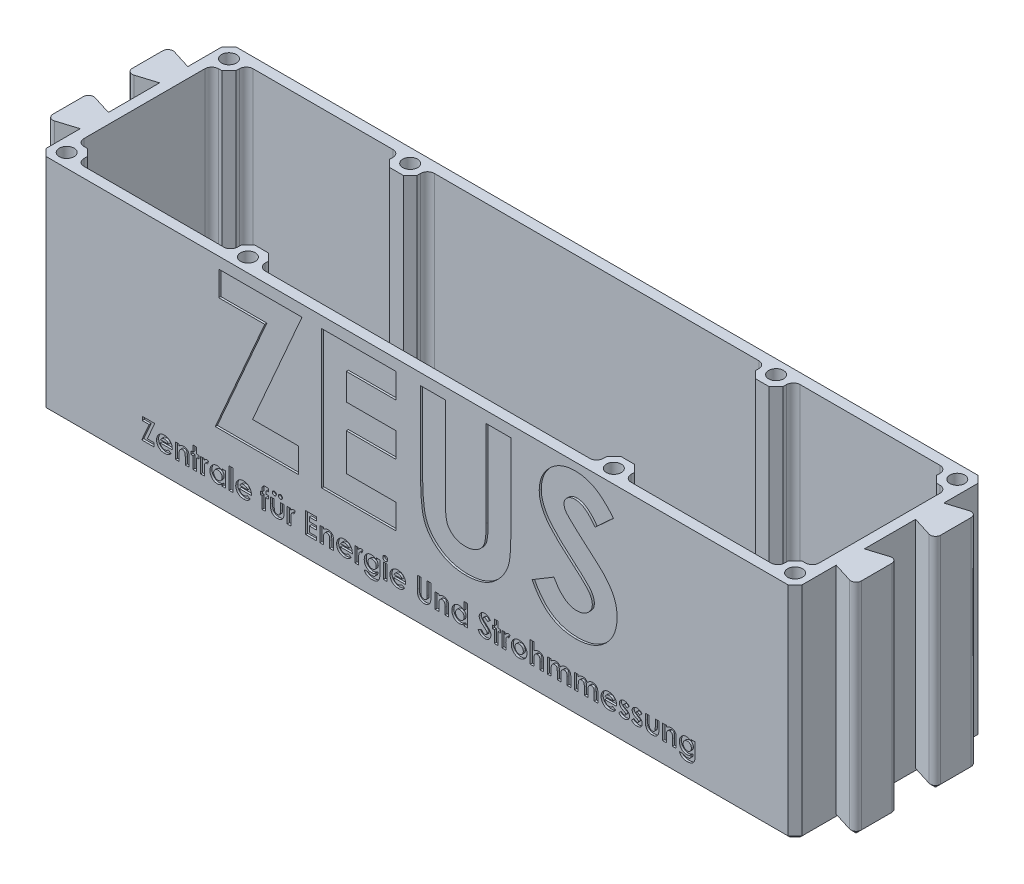
SolidWorks part; units mm, degrees
material "ABS"
ref_plane "Front Plane" through (0, 0, 0) normal (0, 0, 1) x (1, 0, 0)
ref_plane "Top Plane" through (0, 0, 0) normal (0, 1, 0) x (1, 0, 0)
ref_plane "Right Plane" through (0, 0, 0) normal (1, 0, 0) x (0, 0, -1)
sketch "Sketch1" plane through (0, 0, 0) normal (0, 1, 0) x (1, 0, 0)
  line L1 (0, 0) -> (219, 0)
  line L2 (0, 0) -> (0, 55)
  line L3 (0, 55) -> (219, 55)
  line L4 (219, 0) -> (219, 55)
  dimension "D1" = 55
  dimension "D2" = 219
extrude "baseplate" add sketch "Sketch1" along normal blind 4
sketch "Sketch2" plane through (0, 4, 0) normal (0, 1, 0) x (1, 0, 0)
  line L0 (83.3935, 27.5) -> (88.6435, 27.5) construction
  line L1 (83.3935, 49) -> (141.3935, 49) construction
  line L2 (83.3935, 49) -> (83.3935, 6) construction
  line L3 (83.3935, 6) -> (141.3935, 6) construction
  line L4 (141.3935, 49) -> (141.3935, 6) construction
  line L5 (88.6435, 27.5) -> (136.1435, 27.5) construction
  line L6 (136.1435, 27.5) -> (141.3935, 27.5) construction
  line L7 (83.3935, 27.5) -> (0, 27.5) construction
  line L8 (0, 55) -> (0, 0) construction
  line L10 (3, 52) -> (3, 3)
  line L11 (3, 3) -> (216, 3)
  line L12 (216, 3) -> (216, 52)
  line L13 (216, 52) -> (3, 52)
  line L14 (0, 55) -> (0, 0)
  line L15 (0, 0) -> (219, 0)
  line L16 (219, 0) -> (219, 55)
  line L17 (219, 55) -> (0, 55)
  line L18 (0, 55) -> (0, 0)
  line L19 (0, 0) -> (219, 0)
  line L20 (219, 0) -> (219, 55)
  line L21 (219, 55) -> (0, 55)
  circle A0 centre (88.6435, 27.5) radius 2.25 construction
  circle A1 centre (136.1435, 27.5) radius 2.25 construction
  dimension "D3" = 47.5
  dimension "D4" = 4.5
  dimension "D1" = 58
  dimension "D2" = 43
  dimension "D5" = 0
  dimension "D6" = 3
extrude "wall" add sketch "Sketch2" along normal blind 60
chamfer "wall_chamfer" distance 2 angle 45 8 edges at (0, 32, -55) (0, 32, 0) (219, 32, 0) (219, 32, -55) (216, 34, -3) (216, 34, -52) (3, 34, -3) (3, 34, -52)
sketch "Sketch3" plane through (0, 64, 0) normal (0, 1, 0) x (1, 0, 0)
  line L0 (0, 43.081) -> (-5.6527, 44.847)
  line L1 (0, 53) -> (0, 2) construction
  line L2 (-7.6, 43.4153) -> (-7.6, 34.5847)
  line L3 (-5.6527, 33.153) -> (0, 34.919)
  line L4 (0, 34.919) -> (0, 43.081)
  line L5 (109.5, 55) -> (109.5, 3) construction
  line L6 (217, 55) -> (2, 55) construction
  line L7 (5, 3) -> (214, 3) construction
  line L8 (0, 11.919) -> (0, 20.081)
  line L9 (0, 20.081) -> (-5.6527, 21.847)
  line L10 (-7.6, 20.4153) -> (-7.6, 11.5847)
  line L11 (-5.6527, 10.153) -> (0, 11.919)
  line L12 (0, 2) -> (0, 11.919) construction
  line L13 (0, 43.081) -> (0, 53) construction
  line L14 (224.6527, 33.153) -> (219, 34.919)
  line L15 (226.6, 43.4153) -> (226.6, 34.5847)
  line L16 (219, 43.081) -> (224.6527, 44.847)
  line L17 (219, 34.919) -> (219, 43.081)
  line L18 (224.6527, 10.153) -> (219, 11.919)
  line L19 (226.6, 20.4153) -> (226.6, 11.5847)
  line L20 (219, 20.081) -> (224.6527, 21.847)
  line L21 (219, 11.919) -> (219, 20.081)
  arc A0 (-5.6527, 44.847) -> (-7.6, 43.4153) centre (-6.1, 43.4153) ccw
  arc A1 (-5.6527, 33.153) -> (-7.6, 34.5847) centre (-6.1, 34.5847) cw
  arc A2 (-5.6527, 21.847) -> (-7.6, 20.4153) centre (-6.1, 20.4153) ccw
  arc A3 (-5.6527, 10.153) -> (-7.6, 11.5847) centre (-6.1, 11.5847) cw
  arc A4 (224.6527, 33.153) -> (226.6, 34.5847) centre (225.1, 34.5847) ccw
  arc A5 (224.6527, 44.847) -> (226.6, 43.4153) centre (225.1, 43.4153) cw
  arc A6 (224.6527, 10.153) -> (226.6, 11.5847) centre (225.1, 11.5847) ccw
  arc A7 (224.6527, 21.847) -> (226.6, 20.4153) centre (225.1, 20.4153) cw
  dimension "D3" = 1.5
  dimension "D1" = 7.6
  dimension "D2" = 34.7
  dimension "D4" = 2
  dimension "D5" = 23
  dimension "D6" = 8.162
extrude "dovetails" add sketch "Sketch3" against normal up to surface (64 mm away) up to face at (109.5, 0, -27.5)
chamfer "dovetail_chamfers" distance 1.5 angle 45 20 edges at (221.8263, 0, -11.036) (225.9885, 0, -10.3762) (226.6, 0, -16) (225.9885, 0, -21.6238) (221.8263, 0, -20.964) (221.8263, 0, -34.036) (225.9885, 0, -33.3762) (226.6, 0, -39) (225.9885, 0, -44.6238) (221.8263, 0, -43.964) (-2.8263, 0, -43.964) (-6.9885, 0, -44.6238) (-7.6, 0, -39) (-6.9885, 0, -33.3762) (-2.8263, 0, -34.036) (-2.8263, 0, -20.964) (-6.9885, 0, -21.6238) (-7.6, 0, -16) (-6.9885, 0, -10.3762) (-2.8263, 0, -11.036)
chamfer "bottom_chamfer" distance 1 angle 45 12 edges at (219, 0, -27.5) (0, 0, -27.5) (0, 0, -47.2547) (1, 0, -54) (109.5, 0, -55) (218, 0, -54) (219, 0, -47.2547) (0, 0, -7.7453) (1, 0, -1) (109.5, 0, 0) (218, 0, -1) (219, 0, -7.7453)
sketch "Sketch4" plane through (0, 4, 0) normal (0, 1, 0) x (1, 0, 0)
  line L0 (216, 27.5) -> (133.5, 27.5) construction
  line L1 (216, 5) -> (216, 50) construction
  line L2 (133.5, 27.5) -> (85.5, 27.5) construction
  line L3 (85.5, 27.5) -> (3, 27.5) construction
  line L4 (3, 50) -> (3, 5) construction
  line L5 (119.7064, 48.5) -> (119.7064, 27.5) construction
  line L6 (83.5, 48.5) -> (135.5, 48.5)
  line L7 (80.5, 45.5) -> (80.5, 9.5)
  line L8 (83.5, 6.5) -> (135.5, 6.5)
  line L9 (138.5, 45.5) -> (138.5, 9.5)
  line L10 (119.7064, 27.5) -> (119.7064, 6.5) construction
  line L11 (90.5, 35.5) -> (90.5, 19.5)
  line L12 (93.5, 16.5) -> (125.5, 16.5)
  line L13 (128.5, 35.5) -> (128.5, 19.5)
  line L14 (93.5, 38.5) -> (125.5, 38.5)
  line L15 (90.5, 38.5) -> (128.5, 38.5) construction
  line L16 (128.5, 38.5) -> (128.5, 16.5) construction
  line L17 (90.5, 16.5) -> (128.5, 16.5) construction
  line L18 (90.5, 38.5) -> (90.5, 16.5) construction
  circle A0 centre (85.5, 27.5) radius 1.7
  circle A1 centre (133.5, 27.5) radius 1.7
  arc A2 (138.5, 45.5) -> (135.5, 48.5) centre (135.5, 45.5) ccw
  arc A3 (135.5, 6.5) -> (138.5, 9.5) centre (135.5, 9.5) ccw
  arc A4 (83.5, 6.5) -> (80.5, 9.5) centre (83.5, 9.5) cw
  arc A5 (80.5, 45.5) -> (83.5, 48.5) centre (83.5, 45.5) cw
  arc A10 (125.5, 38.5) -> (128.5, 35.5) centre (125.5, 35.5) cw
  arc A11 (128.5, 38.5) -> (128.5, 38.5) centre (128.5, 38.5) ccw construction
  arc A12 (125.5, 16.5) -> (128.5, 19.5) centre (125.5, 19.5) ccw
  arc A13 (128.5, 16.5) -> (128.5, 16.5) centre (128.5, 16.5) ccw construction
  arc A14 (93.5, 16.5) -> (90.5, 19.5) centre (93.5, 19.5) cw
  arc A15 (90.5, 16.5) -> (90.5, 16.5) centre (90.5, 16.5) cw construction
  arc A16 (90.5, 35.5) -> (93.5, 38.5) centre (93.5, 35.5) cw
  arc A17 (90.5, 38.5) -> (90.5, 38.5) centre (90.5, 38.5) cw construction
  point P19 (138.5, 48.5)
  point P22 (138.5, 6.5)
  point P27 (80.5, 48.5)
  dimension "D1" = 48
  dimension "D2" = 3.4
  dimension "D5" = 5
  dimension "D6" = 3
  dimension "D8" = 3
  dimension "D3" = 42
  dimension "D4" = 58
  dimension "D7" = 10
extrude "ssr_mount_plate" add sketch "Sketch4" along normal blind 2
sketch "Sketch5" plane through (0, 4, 0) normal (0, 1, 0) x (1, 0, 0)
  circle A0 centre (133.5, 27.5) radius 1.7 construction
  circle A1 centre (85.5, 27.5) radius 1.7 construction
  circle A2 centre (133.5, 27.5) radius 1.7
  circle A3 centre (85.5, 27.5) radius 1.7
extrude "ssr_mount_holes" cut sketch "Sketch5" against normal through all
sketch "Sketch6" plane through (0, 64, 0) normal (0, 1, 0) x (1, 0, 0)
  line L0 (214, 52) -> (5, 52) construction
  line L1 (80.5, 3) -> (60.5, 3) construction
  line L2 (80.5, 3) -> (80.5, 52) construction
  line L3 (80.5, 52) -> (60.5, 52) construction
  line L4 (60.5, 3) -> (60.5, 52) construction
  line L5 (5, 3) -> (214, 3) construction
  line L6 (80.5, 45.5) -> (80.5, 9.5) construction
  line L7 (217, 55) -> (2, 55) construction
  line L8 (60.5, 52) -> (52.5, 52)
  line L9 (60.5, 52) -> (60.5, 47)
  line L10 (60.5, 47) -> (52.5, 47)
  line L11 (52.5, 52) -> (52.5, 47)
  line L12 (2, 55) -> (8, 55)
  line L13 (0, 53) -> (0, 47)
  line L14 (0, 47) -> (8, 47)
  line L15 (8, 55) -> (8, 47)
  line L16 (0, 53) -> (0, 43.081) construction
  line L17 (2, 55) -> (0, 53) construction
  line L18 (2, 55) -> (0, 53)
  line L19 (3, 27.5) -> (216, 27.5) construction
  line L20 (3, 50) -> (3, 5) construction
  line L21 (216, 5) -> (216, 50) construction
  line L22 (109.5, 52) -> (109.5, 3) construction
  line L23 (214, 52) -> (5, 52) construction
  line L24 (217, 55) -> (219, 53)
  line L25 (219, 53) -> (219, 47)
  line L26 (219, 47) -> (211, 47)
  line L27 (211, 55) -> (211, 47)
  line L28 (217, 55) -> (211, 55)
  line L29 (158.5, 47) -> (166.5, 47)
  line L30 (166.5, 52) -> (166.5, 47)
  line L31 (158.5, 52) -> (166.5, 52)
  line L32 (158.5, 52) -> (158.5, 47)
  line L33 (217, 0) -> (211, 0)
  line L34 (211, 0) -> (211, 8)
  line L35 (219, 8) -> (211, 8)
  line L36 (219, 2) -> (219, 8)
  line L37 (217, 0) -> (219, 2)
  line L38 (158.5, 3) -> (158.5, 8)
  line L39 (158.5, 3) -> (166.5, 3)
  line L40 (166.5, 3) -> (166.5, 8)
  line L41 (158.5, 8) -> (166.5, 8)
  line L42 (60.5, 8) -> (52.5, 8)
  line L43 (52.5, 3) -> (52.5, 8)
  line L44 (60.5, 3) -> (52.5, 3)
  line L45 (60.5, 3) -> (60.5, 8)
  line L46 (2, 0) -> (0, 2)
  line L47 (0, 2) -> (0, 8)
  line L48 (0, 8) -> (8, 8)
  line L49 (8, 0) -> (8, 8)
  line L50 (2, 0) -> (8, 0)
  line L51 (43.6924, 55) -> (43.6924, 52) construction
  dimension "D1" = 20
  dimension "D2" = 5
  dimension "D3" = 8
  dimension "D4" = 8
  dimension "D5" = 3
extrude "lid_mounting_posts" add sketch "Sketch6" against normal up to surface (60 mm away) up to face at (109.5, 4, -27.5)
hole_wizard "lid_mounting_holes" positions "Sketch8" profile "Sketch10" hole size "Ø4.3" standard "DIN"
sketch "Sketch8" plane through (0, 64, 0) normal (0, 1, 0) x (1, 0, 0)
  line L1 (0, 55) -> (8, 55)
  line L2 (0, 55) -> (0, 47)
  line L3 (0, 47) -> (8, 47)
  line L4 (8, 55) -> (8, 47)
  line L5 (0, 55) -> (8, 47) construction
  line L6 (0, 47) -> (8, 55) construction
  line L9 (217, 55) -> (2, 55) construction
  line L12 (52.5, 55) -> (60.5, 55)
  line L13 (52.5, 55) -> (52.5, 47)
  line L14 (52.5, 47) -> (60.5, 47)
  line L15 (60.5, 55) -> (60.5, 47)
  line L16 (52.5, 55) -> (60.5, 47) construction
  line L17 (52.5, 47) -> (60.5, 55) construction
  line L20 (60.5, 47) -> (60.5, 52) construction
  line L21 (52.5, 47) -> (60.5, 47) construction
  line L24 (52.5, 52) -> (52.5, 47) construction
  line L25 (109.5, 55) -> (109.5, 0) construction
  line L26 (2, 0) -> (217, 0) construction
  line L28 (0, 27.5) -> (219, 27.5) construction
  line L29 (0, 34.919) -> (0, 20.081) construction
  line L30 (219, 20.081) -> (219, 34.919) construction
  line L32 (8, 47) -> (8, 52) construction
  line L33 (3, 47) -> (8, 47) construction
  point P1 (4, 51)
  point P48 (56.5, 51)
  point P131 (215, 51)
  point P132 (162.5, 51)
  point P134 (4, 4)
  point P135 (56.5, 4)
  point P136 (162.5, 4)
  point P137 (215, 4)
sketch "Sketch10" plane through (4, 64, -51) normal (1, 0, 0) x (0, 0, 1)
  line L0 (0, 0) -> (0, 11.2919)
  line L1 (0, 11.2919) -> (2.15, 10)
  line L2 (2.15, 10) -> (2.15, 0)
  line L5 (2.15, 0) -> (0, 0)
  line L10 (0, 11.2919) -> (-2.15, 10) construction
  line L11 (0, -6.35) -> (0, 107.95) construction
  dimension "Hole Dia." = 4.3
  dimension "Hole Depth" = 10
  dimension "Drill Angle" = 118
chamfer "posts_chamfers" distance 2 angle 45 12 edges at (52.5, 34, -8) (158.5, 34, -8) (211, 34, -8) (166.5, 34, -8) (60.5, 34, -8) (8, 34, -8) (211, 34, -47) (166.5, 34, -47) (158.5, 34, -47) (60.5, 34, -47) (52.5, 34, -47) (8, 34, -47)
fillet "posts_filets" radius 2 16 edges at (216, 34, -47) (166.5, 34, -3) (166.5, 34, -52) (216, 34, -8) (211, 34, -3) (158.5, 34, -3) (158.5, 34, -52) (211, 34, -52) (60.5, 34, -3) (52.5, 34, -3) (52.5, 34, -52) (8, 34, -3) (3, 34, -8) (60.5, 34, -52) (8, 34, -52) (3, 34, -47)
sketch "Sketch11" plane through (0, 0, 0) normal (0, 0, 1) x (1, 0, 0)
  line L0 (49.5, 20.75) -> (49.5, 32.75) construction
  line L1 (49.5, 32.75) -> (-7.6, 32.75) construction
  line L2 (-7.6, 1.5) -> (-7.6, 64) construction
  line L3 (49.5, 20.75) -> (169.5, 20.75) construction
  line L4 (109.5, 20.75) -> (109.5, 64) construction
  line L5 (2, 64) -> (217, 64) construction
  line L6 (29.5, 6.75) -> (189.5, 6.75) construction
  line L7 (109.5, 6.75) -> (109.5, 20.75) construction
  text T0 "<b>ZEUS</b>" font "Century Gothic" height 40
  text T1 "<b>Zentrale für Energie Und Strohmmessung</b>" font "Century Gothic" height 6
  dimension "D1" = 12
  dimension "D2" = 120
  dimension "D3" = 160
  dimension "D4" = 14
extrude "Cut-Extrude2" cut sketch "Sketch11" against normal blind 0.6 and the other way through all
equation "\"D2@Sketch6\"=\"D3@Sketch6\"-\"D5@Sketch6\""
equation "\"D4@Sketch6\"=\"D3@Sketch6\""
